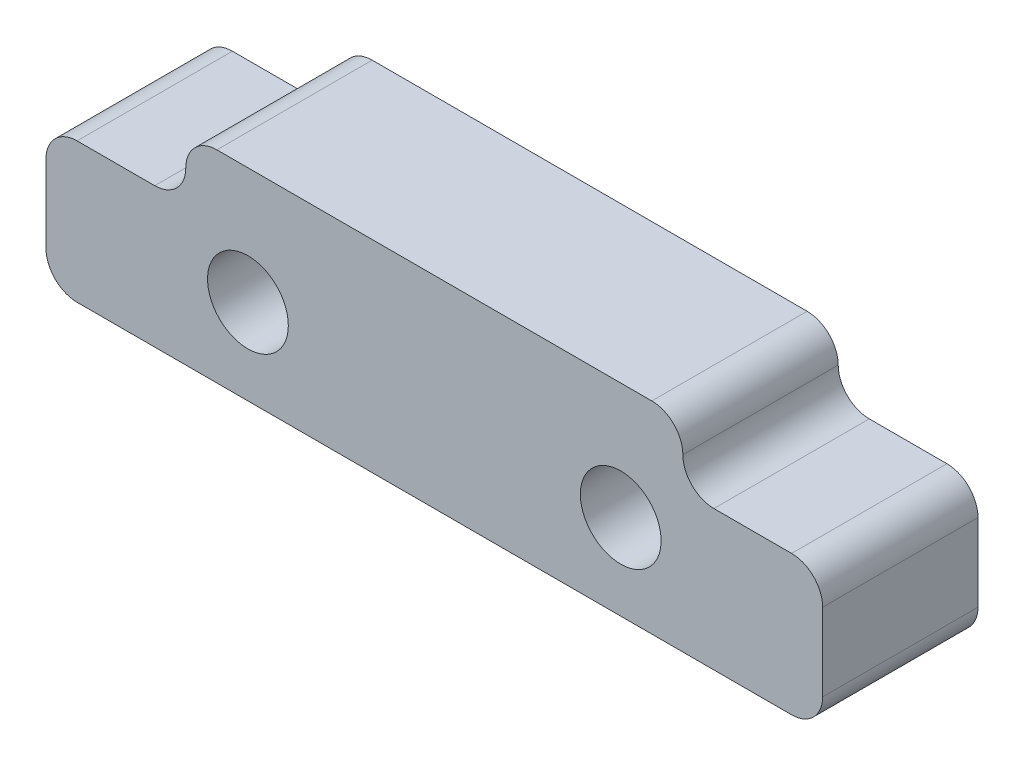
SolidWorks part; units mm, degrees
material "PLA"
ref_plane "前视基准面" through (0, 0, 0) normal (0, 0, 1) x (1, 0, 0)
ref_plane "上视基准面" through (0, 0, 0) normal (0, 1, 0) x (1, 0, 0)
ref_plane "右视基准面" through (0, 0, 0) normal (1, 0, 0) x (0, 0, -1)
sketch "草图1" plane through (0, 0, 0) normal (0, 0, 1) x (1, 0, 0)
  line L0 (0, 0) -> (0, 4.6966) construction
  line L1 (12.5, -2.25) -> (-12.5, -2.25)
  line L2 (12.5, -2.25) -> (12.5, 2.25)
  line L3 (12.5, 2.25) -> (8, 2.25)
  line L4 (-12.5, -2.25) -> (-12.5, 2.25)
  line L5 (12.5, -2.25) -> (-12.5, 2.25) construction
  line L6 (12.5, 2.25) -> (-12.5, -2.25) construction
  line L7 (-8, 2.25) -> (-8, 4.25)
  line L8 (-8, 4.25) -> (8, 4.25)
  line L9 (8, 4.25) -> (8, 2.25)
  line L10 (-8, 2.25) -> (-12.5, 2.25)
  circle A0 centre (-6, 0.5) radius 1.3
  circle A1 centre (6, 0.5) radius 1.3
  point P0 (0, 0)
  dimension "D4" = 2.6
  dimension "D1" = 4.5
  dimension "D2" = 25
  dimension "D3" = 12
  dimension "D5" = 2
  dimension "D6" = 16
  dimension "D7" = 0.5
extrude "凸台-拉伸1" add sketch "草图1" along normal blind 5
fillet "圆角1" radius 1 8 edges at (12.5, -2.25, 2.5) (12.5, 2.25, 2.5) (-12.5, -2.25, 2.5) (-12.5, 2.25, 2.5) (-8, 4.25, 2.5) (8, 4.25, 2.5) (8, 2.25, 2.5) (-8, 2.25, 2.5)
